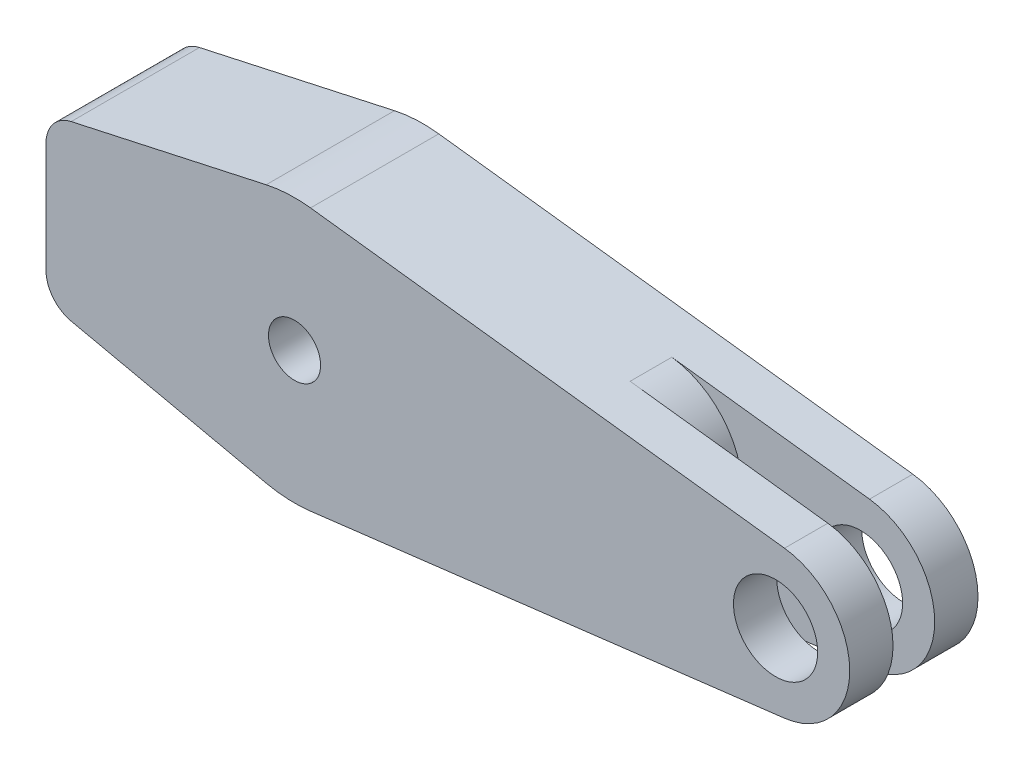
SolidWorks part; units mm, degrees
ref_plane "Front Plane" through (0, 0, 0) normal (0, 0, 1) x (1, 0, 0)
ref_plane "Top Plane" through (0, 0, 0) normal (0, 1, 0) x (1, 0, 0)
ref_plane "Right Plane" through (0, 0, 0) normal (1, 0, 0) x (0, 0, -1)
sketch "Sketch1" plane through (0, 0, 0) normal (0, 0, 1) x (1, 0, 0)
  line L0 (-18.0357, 2.4419) -> (-1.3393, 6.1048)
  line L1 (1.3393, 6.1048) -> (18.0357, 2.4419)
  line L2 (0, 0) -> (0, 14.326) construction
  line L3 (1.3393, -6.1048) -> (18.0357, -2.4419)
  line L4 (-1.3393, -6.1048) -> (-18.0357, -2.4419)
  line L5 (20, 0) -> (20, 7.1993)
  line L6 (-20, 0) -> (-20, 7.1993)
  circle A0 centre (0, 0) radius 6.25
  circle A1 centre (-17.5, 0) radius 2.5
  circle A2 centre (17.5, 0) radius 2.5
  circle A3 centre (0, 0) radius 1.625
  dimension "D1" = 5
  dimension "D2" = 12.5
  dimension "D3" = 3.25
  dimension "D4" = 40
sketch "Sketch2" plane through (0, 0, 0) normal (0, 0, 1) x (1, 0, 0)
  line L1 (-18.0357, 2.4419) -> (-1.3393, 6.1048) construction
  line L5 (-1.3393, -6.1048) -> (-18.0357, -2.4419) construction
  line L6 (1.3393, -6.1048) -> (18.0357, -2.4419) construction
  line L7 (1.3393, 6.1048) -> (18.0357, 2.4419) construction
  line L8 (-18.0357, 2.4419) -> (-1.3393, 6.1048)
  line L9 (-1.3393, -6.1048) -> (-18.0357, -2.4419)
  line L10 (1.3393, -6.1048) -> (18.0357, -2.4419)
  line L11 (1.3393, 6.1048) -> (18.0357, 2.4419)
  line L12 (0.9969, 8.1896) -> (30.5589, 4.5911)
  line L13 (0.9969, -8.1896) -> (30.5589, -4.5911)
  line L14 (-1.7679, -8.0584) -> (-18.4643, -4.3955)
  line L15 (-18.4643, 4.3955) -> (-1.7679, 8.0584)
  circle A2 centre (30, 0) radius 2.625
  circle A3 centre (-17.5, 0) radius 2.5 construction
  circle A4 centre (17.5, 0) radius 2.5 construction
  circle A5 centre (0, 0) radius 6.25 construction
  circle A6 centre (-17.5, 0) radius 2.5
  circle A7 centre (17.5, 0) radius 2.5
  circle A8 centre (0, 0) radius 6.25
  circle A9 centre (-17.5, 0) radius 4.5
  circle A10 centre (0, 0) radius 8.25
  circle A12 centre (30, 0) radius 4.625
  dimension "D1" = 2
  dimension "D2" = 2
  dimension "D4" = 5.25
  dimension "D5" = 2
  dimension "D3" = 30
extrude "Boss-Extrude2" add sketch "Sketch2" along normal blind 8 contours A12 L12 A10 L11 A7 L10 L13 | A7 | A10 L10 A7 L11 | A12 A2 | A8 | L8 A10 L9 A8 | L11 A10 L8 A8 | L9 A10 L10 A8 | L10 A10 L11 A8 | A10 L8 A9 L9 | L8 A9 L9 A6 | L9 A9 L8 A6 | A10 L15 A9 L8 | A10 L9 A9 L14 | A6 region at (-20.1179, 0, 0) region at (-14.6238, 0, 0) region at (-10.4033, 5.2527, 0) region at (-10.4488, 0, 0) region at (0, 6.6883, 0) region at (-6.3049, 0, 0) region at (-10.4033, -5.2527, 0) region at (0, 0, 0) region at (0, -6.6883, 0) region at (6.3049, 0, 0) region at (15.737, 6.0548, 0) region at (11.4415, 0, 0) region at (33.3644, 2.9797, 0) region at (17.5, 0, 0)
extrude "Cut-Extrude5" cut sketch "Sketch1" along normal blind 3.15 contours L3 A2 L1 A0 | A3 A0 | A1 L4 A0 L0 | A1 | A2 | A3 region at (-9.9667, 0, 0) region at (-17.5, 0, 0) region at (0, 6.0732, 0) region at (9.9667, 0, 0) region at (17.5, 0, 0) region at (0, 0, 0)
sketch "Sketch6" plane through (0, 0, 0) normal (0, 1, 0) x (1, 0, 0)
  line L0 (34.625, -8) -> (34.625, 0) construction
  line L1 (46.625, -2.7) -> (22.625, -2.7)
  line L2 (46.625, -2.7) -> (46.625, -5.3)
  line L3 (46.625, -5.3) -> (22.625, -5.3)
  line L4 (22.625, -2.7) -> (22.625, -5.3)
  line L5 (46.625, -2.7) -> (22.625, -5.3) construction
  line L6 (46.625, -5.3) -> (22.625, -2.7) construction
  point P0 (34.625, -4)
  point P7 (34.625, -2.7)
  dimension "D1" = 12
  dimension "D2" = 2.6
extrude "Cut-Extrude6" cut sketch "Sketch6" against normal through all both and the other way through all
fillet "Fillet1" radius 5 2 edges at (22.625, -5.5569, 4) (22.625, 5.5569, 4)
extrude "Cut-Extrude7" cut sketch "Sketch1<7>" along normal through all both contours A3
sketch "Sketch1<7>" plane through (0, 0, 0) normal (0, 0, 1) x (1, 0, 0) same geometry as "Sketch1"
sketch "Sketch7" plane through (0, 0, 0) normal (0, 0, 1) x (1, 0, 0)
  line L1 (-42.471, 11.5023) -> (-15.5, 11.5023)
  line L2 (-42.471, 11.5023) -> (-42.471, -11.5023)
  line L3 (-42.471, -11.5023) -> (-15.5, -11.5023)
  line L4 (-15.5, 11.5023) -> (-15.5, -11.5023)
  line L5 (-42.471, 11.5023) -> (-15.5, -11.5023) construction
  line L6 (-42.471, -11.5023) -> (-15.5, 11.5023) construction
  arc A0 (-18.4643, 4.3955) -> (-18.4643, -4.3955) centre (-17.5, 0) ccw construction
  point P0 (-28.9855, 0)
  dimension "D1" = 2
extrude "Cut-Extrude8" cut sketch "Sketch7" along normal through all
fillet "Fillet2" radius 2 2 edges at (-15.5, 5.0458, 4) (-15.5, -5.0458, 4)
equation "\"thick\"= 8mm"
equation "\"D1@Boss-Extrude2\"=\"thick\""
equation "\"D1@Cut-Extrude5\"=(\"thick\"/2) - 0.85"
